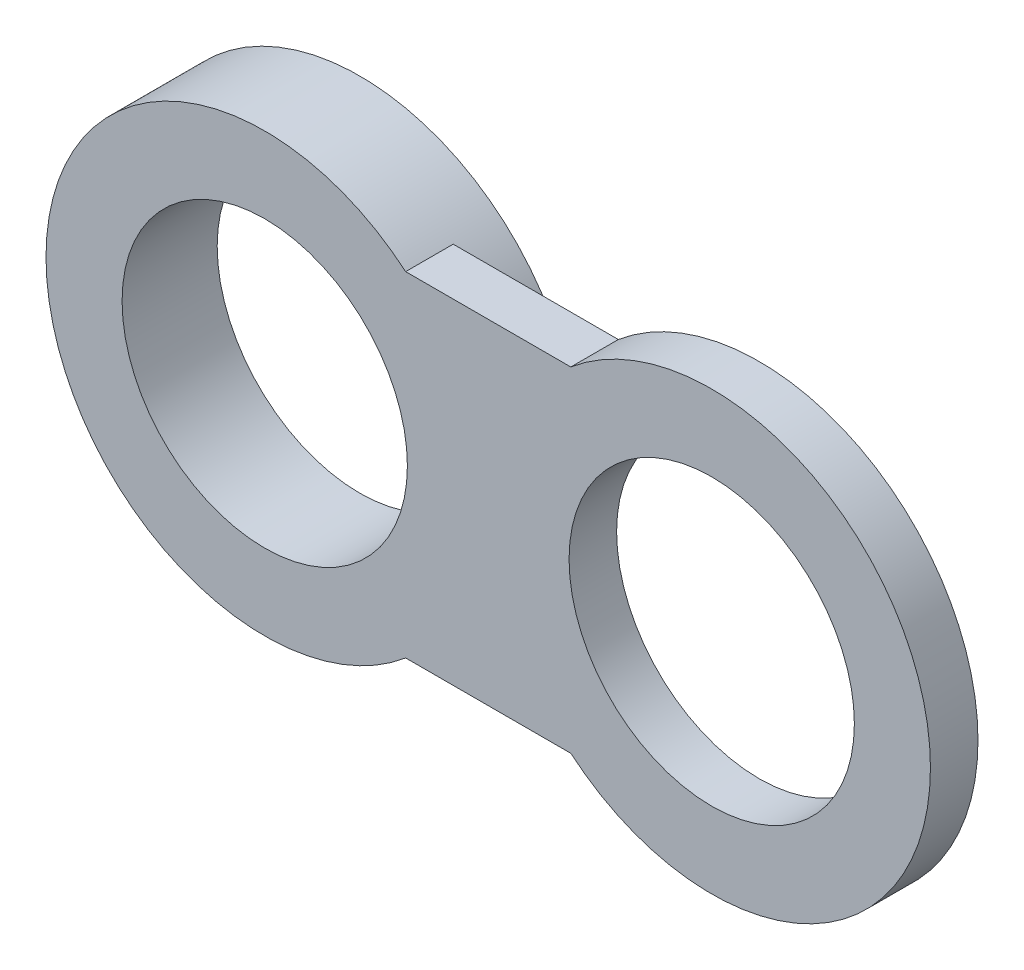
SolidWorks part; units mm, degrees
ref_plane "Front Plane" through (0, 0, 0) normal (0, 0, 1) x (1, 0, 0)
ref_plane "Top Plane" through (0, 0, 0) normal (0, 1, 0) x (1, 0, 0)
ref_plane "Right Plane" through (0, 0, 0) normal (1, 0, 0) x (0, 0, -1)
sketch "Sketch3" plane through (0, 0, 0) normal (0, 0, 1) x (1, 0, 0)
  line L0 (0, 0) -> (-250, 0) construction
  line L1 (650.4122, 0) -> (-650.4122, 0) construction
  dimension "D1" = 250
sketch "Sketch4" plane through (0, 0, 0) normal (0, 0, 1) x (1, 0, 0)
  line L0 (0, 0) -> (220, 0) construction
  line L1 (0, 0) -> (0, 175.9092) construction
  line L2 (0, -55) -> (0, 55) construction
  line L3 (0, 175.9092) -> (0, 0) construction
  line L4 (0, 175.9092) -> (-101.8246, 175.9092)
  line L5 (-101.8246, 175.9092) -> (71.8246, 175.9092)
  line L6 (0, 0) -> (0, -175.9092) construction
  line L7 (0, -175.9092) -> (71.8246, -175.9092)
  line L8 (71.8246, -175.9092) -> (-101.8246, -175.9092)
  circle A0 centre (-250, 0) radius 230
  circle A1 centre (220, 0) radius 230
  circle A2 centre (-250, 0) radius 150
  circle A3 centre (220, 0) radius 150
  dimension "D1" = 220
  dimension "D4" = 300
  dimension "D5" = 300
  dimension "D6" = 460
  dimension "D7" = 460
  dimension "D2" = 173.6492
  dimension "D3" = 173.6492
extrude "Boss-Extrude1" add sketch "Sketch4" along normal blind 25 and the other way blind 25 contours A0 A2 | A1 A3 | A1 L5 L4 A0 L8 L7 region at (-15, 0, 0) region at (-47.3555, 94.2606, 0) region at (314.2606, 202.6445, 0)
extrude "Boss-Extrude2" add sketch "Sketch4<4>" against normal blind 75 contours A0 A2 region at (-47.3555, 94.2606, 0)
sketch "Sketch4<4>" plane through (0, 0, 0) normal (0, 0, 1) x (1, 0, 0) same geometry as "Sketch4"
